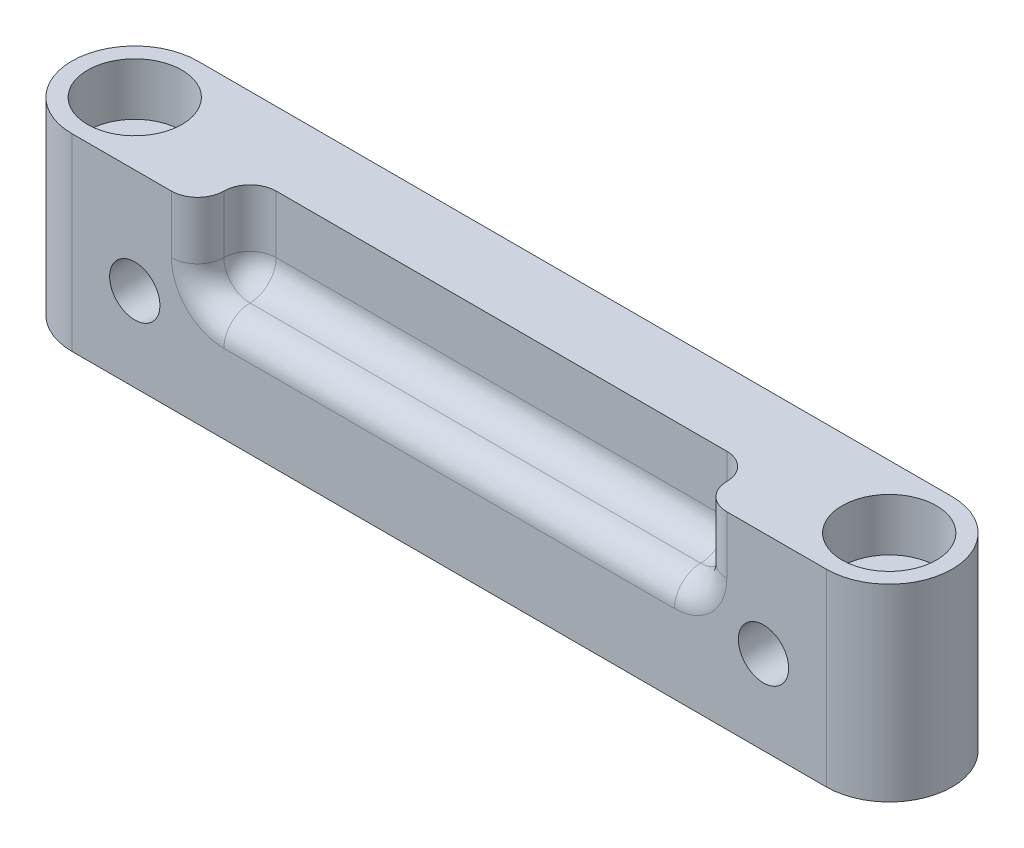
SolidWorks part; units mm, degrees
material "PET"
ref_plane "Front Plane" through (0, 0, 0) normal (0, 0, 1) x (1, 0, 0)
ref_plane "Top Plane" through (0, 0, 0) normal (0, 1, 0) x (1, 0, 0)
ref_plane "Right Plane" through (0, 0, 0) normal (1, 0, 0) x (0, 0, -1)
sketch "Sketch1" plane through (0, 0, 0) normal (0, 1, 0) x (1, 0, 0)
  line L0 (36, 0) -> (-36, 0) construction
  line L1 (36, -6) -> (-36, -6)
  line L2 (36, 6) -> (-36, 6)
  arc A0 (36, -6) -> (36, 6) centre (36, 0) ccw
  arc A1 (-36, 6) -> (-36, -6) centre (-36, 0) ccw
  circle A2 centre (-36, 0) radius 2.4
  circle A3 centre (36, 0) radius 2.4
  point P2 (0, 0)
  dimension "D3" = 4.8
  dimension "D1" = 12
  dimension "D2" = 72
extrude "Boss-Extrude1" add sketch "Sketch1" along normal mid plane 18
sketch "Sketch2" plane through (0, 9, 0) normal (0, 1, 0) x (1, 0, 0)
  circle A0 centre (-36, 0) radius 4.5
  circle A1 centre (36, 0) radius 4.5
  dimension "D1" = 9
extrude "Cut-Extrude1" cut sketch "Sketch2" against normal blind 5
sketch "Sketch3" plane through (0, 9, 0) normal (0, 1, 0) x (1, 0, 0)
  line L0 (-36, -6) -> (36, -6) construction
  line L1 (24, -1) -> (-24, -1)
  line L2 (24, -1) -> (24, -6)
  line L3 (24, -6) -> (-24, -6)
  line L4 (-24, -1) -> (-24, -6)
  line L5 (24, -1) -> (-24, -6) construction
  line L6 (24, -6) -> (-24, -1) construction
  line L7 (0, 0) -> (0, -3.5) construction
  point P0 (0, -3.5)
  dimension "D1" = 5
  dimension "D2" = 48
extrude "Cut-Extrude2" cut sketch "Sketch3" against normal blind 8
fillet "Fillet1" radius 2.5 8 edges at (0, 1, 6) (-24, 1, 3.5) (24, 1, 3.5) (24, 5, 6) (24, 5, 1) (-24, 5, 1) (-24, 5, 6) (0, 1, 1)
sketch "Sketch4" plane through (0, 0, 6) normal (0, 0, 1) x (1, 0, 0)
  line L0 (-30, -1) -> (30, -1) construction
  line L1 (0, -1) -> (0, 0) construction
  line L2 (-36, -9) -> (36, -9) construction
  circle A0 centre (-30, -1) radius 2.4
  circle A1 centre (30, -1) radius 2.4
  dimension "D1" = 4.8
  dimension "D2" = 60
  dimension "D3" = 8
extrude "Cut-Extrude3" cut sketch "Sketch4" against normal through all
